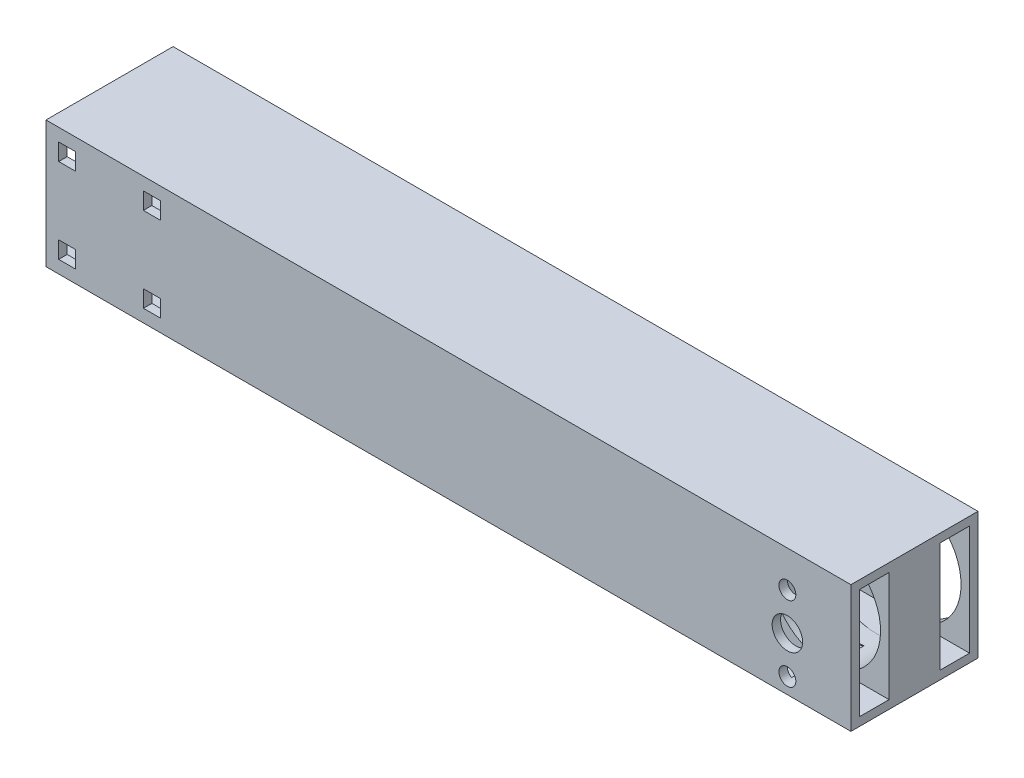
SolidWorks part; units mm, degrees
material "PLA 15%"
ref_plane "Front Plane" through (0, 0, 0) normal (0, 0, 1) x (1, 0, 0)
ref_plane "Top Plane" through (0, 0, 0) normal (0, 1, 0) x (1, 0, 0)
ref_plane "Right Plane" through (0, 0, 0) normal (1, 0, 0) x (0, 0, -1)
sketch "Sketch1" plane through (0, 0, 0) normal (1, 0, 0) x (0, 0, -1)
  line L1 (-15, -15) -> (15, -15)
  line L2 (-15, -15) -> (-15, 15)
  line L3 (-15, 15) -> (15, 15)
  line L4 (15, -15) -> (15, 15)
  line L5 (-15, -15) -> (15, 15) construction
  line L6 (-15, 15) -> (15, -15) construction
  line L11 (-5.1844, 5.1844) -> (5.1844, -5.1844) construction
  line L12 (-5.1844, -5.1844) -> (5.1844, 5.1844) construction
  line L13 (-13, 13) -> (-6, 13)
  line L14 (-13, 13) -> (-13, -13)
  line L15 (-13, -13) -> (-6, -13)
  line L16 (-6, 13) -> (-6, -13)
  line L17 (13, 13) -> (6, 13)
  line L18 (13, 13) -> (13, -13)
  line L19 (13, -13) -> (6, -13)
  line L20 (6, 13) -> (6, -13)
  point P0 (0, 0)
  point P7 (0, 0)
  dimension "D1" = 30
  dimension "D2" = 30
  dimension "D3" = 2
  dimension "D4" = 7
  dimension "D5" = 2
  dimension "D6" = 7
  dimension "D7" = 2
  dimension "D8" = 2
extrude "Boss-Extrude3" add sketch "Sketch1" along normal blind 110 and the other way blind 80
sketch "Sketch6" plane through (0, 0, -15) normal (0, 0, -1) x (-1, 0, 0)
  line L0 (-110, -15) -> (-110, 15) construction
  line L2 (-110, 0) -> (80, 0) construction
  line L3 (80, -15) -> (80, 15) construction
  circle A0 centre (-95, 0) radius 13
  dimension "D2" = 26
  dimension "D1" = 15
extrude "Cut-Extrude5" cut sketch "Sketch6" against normal blind 23
sketch "Sketch8" plane through (0, 0, 15) normal (0, 0, 1) x (1, 0, 0)
  line L0 (110, 15) -> (110, -15) construction
  circle A0 centre (95, -2.4256) radius 3.6
  circle A1 centre (95, 6.4244) radius 2
  circle A2 centre (95, -11.2756) radius 2
  point P5 (95, -11.1718)
  point P8 (95, 6.4244)
  dimension "D2" = 7.2
  dimension "D5" = 4
  dimension "D6" = 4
  dimension "D1" = 15
  dimension "D3" = 8.85
  dimension "D4" = 8.85
extrude "Cut-Extrude6" cut sketch "Sketch8" against normal blind 17
sketch "Sketch9" plane through (-80, 0, 0) normal (-1, 0, 0) x (0, 0, 1)
  line L0 (-6, 13) -> (6, 13)
  line L1 (-6, -13) -> (6, -13)
  line L2 (-6, 13) -> (-6, -13)
  line L3 (6, 13) -> (6, -13)
extrude "Cut-Extrude7" cut sketch "Sketch9" against normal blind 106
sketch "Sketch12" plane through (0, 0, 15) normal (0, 0, 1) x (1, 0, 0)
  line L0 (-80, 15) -> (110, 15) construction
  line L1 (-80, 15) -> (-80, -15) construction
  line L2 (-80, 15) -> (-50, 15) construction
  line L3 (-50, 15) -> (-50, -15) construction
  line L5 (-80, -15) -> (110, -15) construction
  line L6 (-77, 8) -> (-73, 8)
  line L7 (-77, 8) -> (-77, 12)
  line L8 (-77, 12) -> (-73, 12)
  line L9 (-73, 8) -> (-73, 12)
  line L10 (-77, 8) -> (-73, 12) construction
  line L11 (-77, 12) -> (-73, 8) construction
  line L12 (-57.0136, 8) -> (-52.9864, 8)
  line L13 (-57.0136, 8) -> (-57.0136, 12)
  line L14 (-57.0136, 12) -> (-52.9864, 12)
  line L15 (-52.9864, 8) -> (-52.9864, 12)
  line L16 (-57.0136, 8) -> (-52.9864, 12) construction
  line L17 (-57.0136, 12) -> (-52.9864, 8) construction
  line L18 (-57, -12) -> (-53, -12)
  line L19 (-57, -12) -> (-57, -8)
  line L20 (-57, -8) -> (-53, -8)
  line L21 (-53, -12) -> (-53, -8)
  line L22 (-57, -12) -> (-53, -8) construction
  line L23 (-57, -8) -> (-53, -12) construction
  line L24 (-77, -12) -> (-73, -12)
  line L25 (-77, -12) -> (-77, -8)
  line L26 (-77, -8) -> (-73, -8)
  line L27 (-73, -12) -> (-73, -8)
  line L28 (-77, -12) -> (-73, -8) construction
  line L29 (-77, -8) -> (-73, -12) construction
  circle A2 centre (-55, 10) radius 2
  circle A3 centre (-75, -10) radius 2
  circle A4 centre (-55, -10) radius 2
  dimension "D3" = 4
  dimension "D7" = 4
  dimension "D9" = 4
  dimension "D11" = 4
  dimension "D2" = 4
  dimension "D4" = 5
  dimension "D5" = 30
  dimension "D6" = 5
  dimension "D8" = 5
  dimension "D10" = 5
  dimension "D12" = 20
  dimension "D13" = 5
  dimension "D14" = 4
extrude "Cut-Extrude8" cut sketch "Sketch12" against normal blind 40 contours L8 L9 L6 L7 | L14 L15 L12 L13 | L20 L21 L18 L19 | L26 L27 L24 L25
